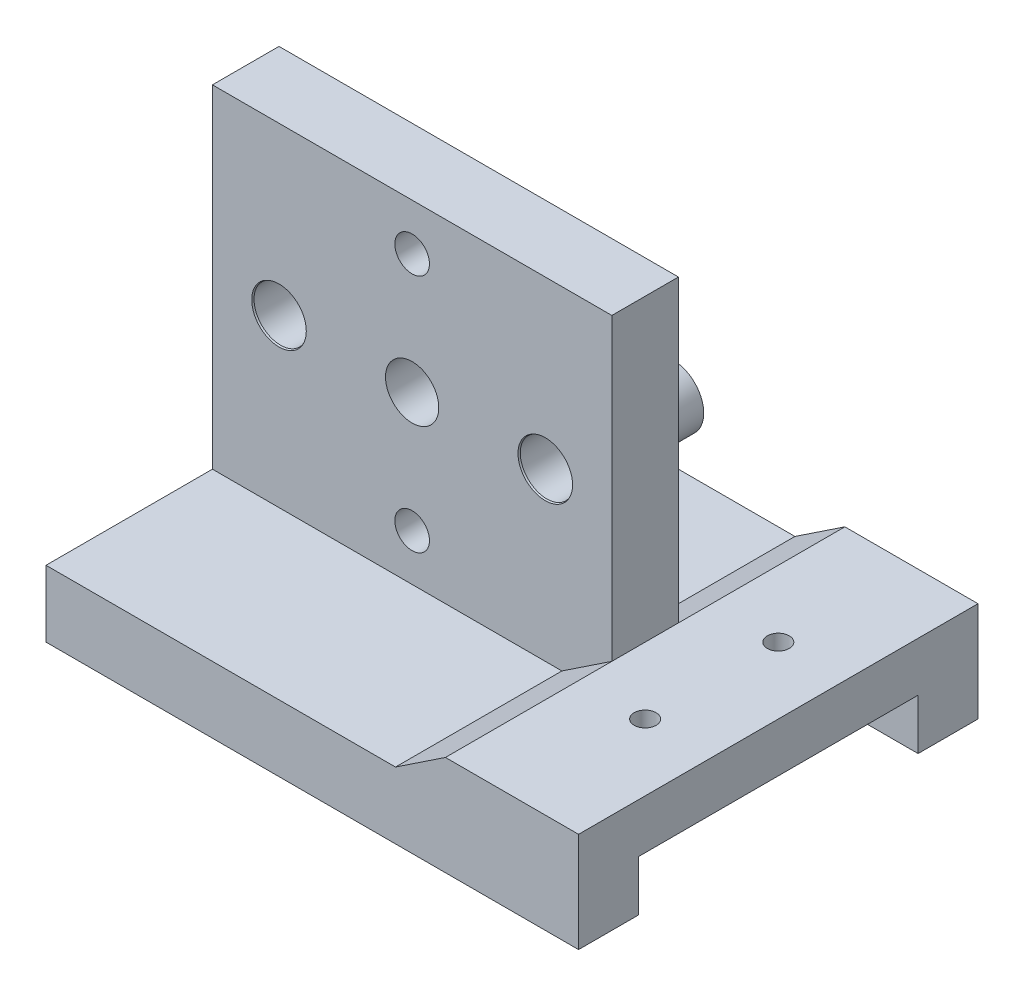
SolidWorks part; units mm, degrees
ref_plane "前视基准面" through (0, 0, 0) normal (0, 0, 1) x (1, 0, 0)
ref_plane "上视基准面" through (0, 0, 0) normal (0, 1, 0) x (1, 0, 0)
ref_plane "右视基准面" through (0, 0, 0) normal (1, 0, 0) x (0, 0, -1)
other "Configuration Table"
sketch "草图1" plane through (0, 0, 0) normal (0, 0, 1) x (1, 0, 0)
  line L1 (-30, -25) -> (30, -25)
  line L2 (-30, -25) -> (-30, 25)
  line L3 (-30, 25) -> (30, 25)
  line L4 (30, -25) -> (30, 25)
  line L5 (-30, -25) -> (30, 25) construction
  line L6 (-30, 25) -> (30, -25) construction
  point P0 (0, 0)
  dimension "D1" = 50
  dimension "D2" = 60
extrude "凸台-拉伸1" add sketch "草图1" along normal blind 10
hole_wizard "孔2" positions "草图4" profile "草图5" legacy end condition through all
sketch "草图4" plane through (0, 0, 10) normal (0, 0, 1) x (1, 0, 0)
  point P0 (20, 0)
  point P2 (-20, 0)
  dimension "D1" = 20
  dimension "D2" = 20
sketch "草图5" plane through (20, 0, 10) normal (1, 0, 0) x (0, -1, 0)
  line L0 (0, 0) -> (0, 10)
  line L1 (0, 10) -> (4, 10)
  line L2 (4, 10) -> (4, 0.2414)
  line L3 (4, 0.2414) -> (4.1, 0)
  line L4 (4.1, 0) -> (0, 0)
  line L5 (0, -6.4453) -> (0, 115.525) construction
  line L6 (-4, 0.2414) -> (-4.1, 0) construction
  dimension "直径" = 8
  dimension "深度" = 10
  dimension "锥坑角度" = 45
  dimension "锥坑直径" = 8.2
hole_wizard "孔3" positions "草图6" profile "草图7" legacy end condition through all
sketch "草图6" plane through (0, 0, 0) normal (0, 0, -1) x (-1, 0, 0)
  point P0 (0, 18)
  point P2 (0, -18)
  dimension "D1" = 18
  dimension "D2" = 18
sketch "草图7" plane through (0, 18, 0) normal (1, 0, 0) x (0, 1, 0)
  line L0 (0, 0) -> (0, 10)
  line L1 (0, 10) -> (2.6, 10)
  line L2 (2.6, 10) -> (2.6, 0)
  line L3 (2.6, 0) -> (0, 0)
  line L4 (0, 110) -> (0, -10) construction
  dimension "直径" = 5.2
  dimension "深度" = 10
sketch "草图8" plane through (0, -25, 0) normal (0, -1, 0) x (1, 0, 0)
  line L1 (-30, -25) -> (50, -25)
  line L2 (-30, -25) -> (-30, 35)
  line L3 (-30, 35) -> (50, 35)
  line L4 (50, -25) -> (50, 35)
  point P0 (0, 5)
  dimension "D1" = 60
  dimension "D2" = 80
extrude "凸台-拉伸2" add sketch "草图8" along normal blind 10
ref_plane "基准面1" through (0, 0, 5) normal (0, 0, 1) x (1, 0, 0)
sketch "草图11" plane through (0, 0, 5) normal (0, 0, 1) x (1, 0, 0)
  line L1 (50, -35) -> (30, -35)
  line L2 (50, -35) -> (50, -27.4)
  line L3 (50, -27.4) -> (30, -27.4)
  line L4 (30, -35) -> (30, -27.4)
  dimension "D1" = 7.6
extrude "切除-拉伸1" cut sketch "草图11" against normal mid plane 42
sketch "草图12" plane through (0, 0, 5) normal (0, 0, 1) x (1, 0, 0)
  line L0 (30, -25) -> (30, 25) construction
  line L1 (50, -25) -> (30, -25)
  line L2 (50, -25) -> (50, -20)
  line L3 (50, -20) -> (30, -20)
  line L4 (30, -25) -> (30, -20)
  dimension "D1" = 5
extrude "凸台-拉伸4" add sketch "草图12" along normal mid plane 60
hole_wizard "孔4" positions "草图13" profile "草图14" legacy end condition through all
sketch "草图13" plane through (0, -20, 0) normal (0, 1, 0) x (1, 0, 0)
  point P0 (40, -15)
  point P3 (40, 5)
sketch "草图14" plane through (40, -20, 15) normal (1, 0, 0) x (0, 0, 1)
  line L0 (0, 0) -> (0, 15)
  line L1 (0, 15) -> (1.65, 15)
  line L2 (1.65, 15) -> (1.65, 0)
  line L3 (1.65, 0) -> (0, 0)
  line L4 (0, 110) -> (0, -10) construction
  dimension "直径" = 3.3
  dimension "深度" = 15
sketch "草图15" plane through (0, 0, 35) normal (0, 0, 1) x (1, 0, 0)
  line L0 (30, -20) -> (22.5, -25)
  line L1 (-30, -25) -> (30, -25) construction
  line L2 (30, -25) -> (30, -20) construction
  line L3 (30, -20) -> (30, -25)
  line L4 (30, -25) -> (22.5, -25)
  dimension "D1" = 7.5
extrude "凸台-拉伸5" add sketch "草图15" against normal through all
fillet "圆角1" [suppressed] type full round
chamfer "倒角1" [suppressed] distance 1 angle 45
hole_wizard "孔5" positions "草图16" profile "草图18" legacy end condition through all
sketch "草图16" plane through (0, 0, 0) normal (0, 0, -1) x (-1, 0, 0)
  point P0 (0, 0)
sketch "草图18" plane through (0, 0, 0) normal (1, 0, 0) x (0, 1, 0)
  line L0 (0, 0) -> (0, 35)
  line L1 (0, 35) -> (4, 35)
  line L2 (4, 35) -> (4, 0.6036)
  line L3 (4, 0.6036) -> (4.25, 0)
  line L4 (4.25, 0) -> (0, 0)
  line L5 (0, -6.4453) -> (0, 115.525) construction
  line L6 (-4, 0.6036) -> (-4.25, 0) construction
  dimension "直径" = 8
  dimension "深度" = 35
  dimension "锥坑角度" = 45
  dimension "锥坑直径" = 8.5
sketch "草图19" plane through (0, 0, 0) normal (0, 0, -1) x (-1, 0, 0)
  circle A0 centre (0, 0) radius 4.25
  circle A1 centre (0, 0) radius 4.75
  dimension "D1" = 8.5
  dimension "D2" = 9.5
hole_wizard "孔6" positions "草图20" profile "草图21" legacy end condition through all
sketch "草图20" plane through (0, 0, 0) normal (0, 0, -1) x (-1, 0, 0)
  point P0 (-20, 0)
  point P3 (20, 0)
sketch "草图21" plane through (20, 0, 0) normal (1, 0, 0) x (0, 1, 0)
  line L0 (0, 0) -> (0, 35)
  line L1 (0, 35) -> (4, 35)
  line L2 (4, 35) -> (4, 0.2414)
  line L3 (4, 0.2414) -> (4.1, 0)
  line L4 (4.1, 0) -> (0, 0)
  line L5 (0, -6.4453) -> (0, 115.525) construction
  line L6 (-4, 0.2414) -> (-4.1, 0) construction
  dimension "直径" = 8
  dimension "深度" = 35
  dimension "锥坑角度" = 45
  dimension "锥坑直径" = 8.2
sketch "草图22" plane through (0, 0, 0) normal (0, 0, -1) x (-1, 0, 0)
  circle A0 centre (-20, 0) radius 4.1
  circle A1 centre (-20, 0) radius 4.6
  circle A2 centre (20, 0) radius 4.1
  circle A3 centre (20, 0) radius 4.6
  dimension "D1" = 8.2
  dimension "D2" = 9.2
  dimension "D3" = 8.2
  dimension "D4" = 9.2
extrude "凸台-拉伸7" add sketch "草图22" along normal blind 9.2
